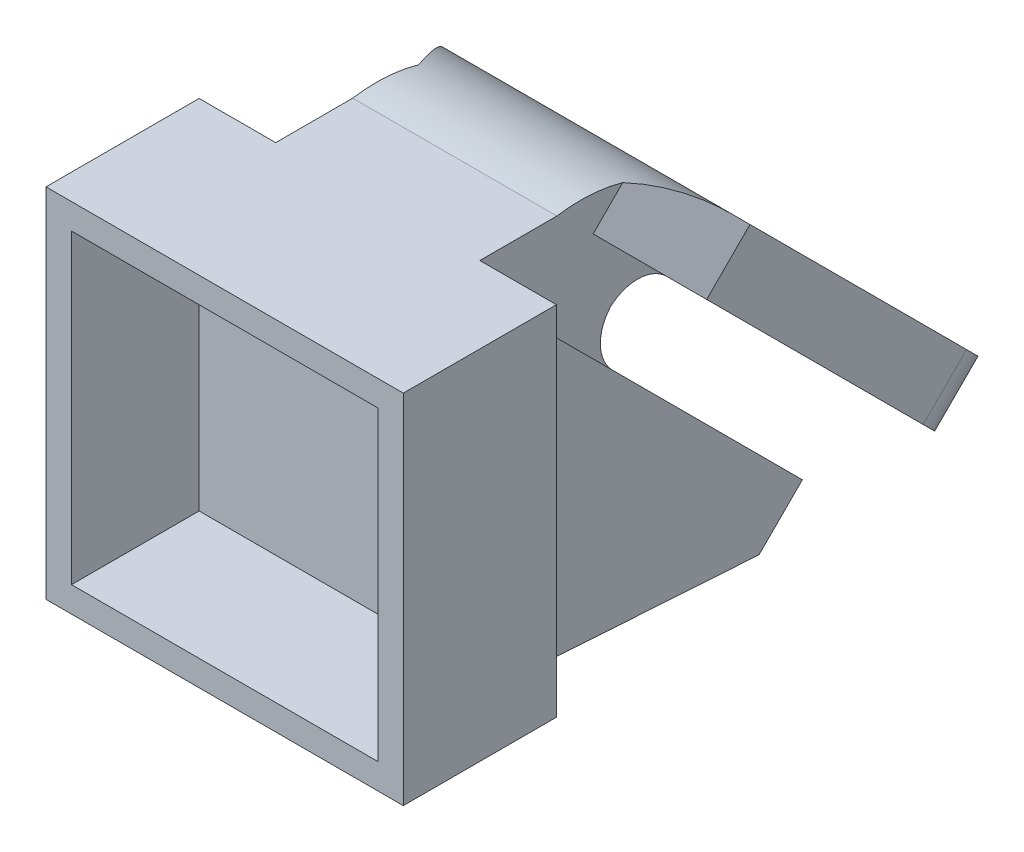
SolidWorks part; units mm, degrees
ref_plane "Piano frontale" through (0, 0, 0) normal (0, 0, 1) x (1, 0, 0)
ref_plane "Piano superiore" through (0, 0, 0) normal (0, 1, 0) x (1, 0, 0)
ref_plane "Piano destro" through (0, 0, 0) normal (1, 0, 0) x (0, 0, -1)
sketch "Schizzo1" plane through (0, 0, 0) normal (0, 0, 1) x (1, 0, 0)
  line L1 (30, -30) -> (-30, -30)
  line L2 (30, -30) -> (30, 30)
  line L3 (30, 30) -> (-30, 30)
  line L4 (-30, -30) -> (-30, 30)
  line L5 (30, -30) -> (-30, 30) construction
  line L6 (30, 30) -> (-30, -30) construction
  line L7 (35, -35) -> (-35, -35)
  line L8 (35, -35) -> (35, 35)
  line L9 (35, 35) -> (-35, 35)
  line L10 (-35, -35) -> (-35, 35)
  line L11 (35, -35) -> (-35, 35) construction
  line L12 (35, 35) -> (-35, -35) construction
  point P0 (0, 0)
  point P6 (0, 0)
  dimension "D1" = 60
  dimension "D2" = 60
  dimension "D3" = 5
  dimension "D4" = 5
extrude "Estrusione-Estrusione1" add sketch "Schizzo1" along normal blind 30
sketch "Schizzo2" plane through (0, 0, 0) normal (0, 0, 1) x (1, 0, 0)
  line L0 (35, 35) -> (-35, 35) construction
  line L1 (35, -35) -> (-35, -35)
  line L2 (35, -35) -> (35, 35)
  line L3 (35, 35) -> (-35, 35)
  line L4 (-35, -35) -> (-35, 35)
  line L5 (35, -35) -> (-35, 35) construction
  line L6 (35, 35) -> (-35, -35) construction
  line L7 (-35, 35) -> (-35, -35) construction
  point P0 (0, 0)
extrude "Estrusione-Estrusione2" add sketch "Schizzo2" along normal blind 5
sketch "Schizzo3" plane through (0, 0, 0) normal (0, 0, -1) x (-1, 0, 0)
  line L0 (-35, 35) -> (35, 35) construction
  line L1 (-20, 35) -> (20, 35)
  line L2 (-20, 35) -> (-20, 15)
  line L3 (-20, 15) -> (20, 15)
  line L4 (20, 35) -> (20, 15)
  point P6 (0, 15)
  dimension "D1" = 20
  dimension "D2" = 40
extrude "Estrusione-Estrusione3" add sketch "Schizzo3" along normal blind 25
chamfer "Smusso1" distance 20 angle 45 1 edges at (0, 15, -25)
ref_plane "Piano1" through (0, 5, 5) normal (0, -0.7071, -0.7071) x (-1, 0, 0)
sketch "Schizzo4" plane through (0, 5, 5) normal (0, -0.7071, -0.7071) x (-1, 0, 0)
  line L0 (20, 42.4264) -> (20, 14.1421) construction
  line L9 (20, 42.4264) -> (-20, 42.4264) construction
  line L10 (-30, 47.7843) -> (30, 47.7843)
  line L11 (-30, 47.7843) -> (-30, 35.7843)
  line L12 (-30, 35.7843) -> (30, 35.7843)
  line L13 (30, 47.7843) -> (30, 35.7843)
  line L14 (-20, 20.7843) -> (20, 20.7843)
  line L15 (-20, 20.7843) -> (-20, 8.7843)
  line L16 (-20, 8.7843) -> (20, 8.7843)
  line L17 (20, 20.7843) -> (20, 8.7843)
  line L18 (0, 35.7843) -> (0, 20.7843) construction
  point P8 (0, 28.2843)
  point P12 (20, 28.2843)
  point P15 (0, 42.4264)
  point P16 (0, 35.7843)
  point P17 (0, 20.7843)
  dimension "D1" = 60
  dimension "D2" = 12
  dimension "D3" = 12
  dimension "D4" = 15
  dimension "D5" = 40
extrude "Estrusione-Estrusione4" add sketch "Schizzo4" along normal blind 80
sketch "Schizzo19" plane through (0, -51.5685, -51.5685) normal (0, -0.7071, -0.7071) x (1, 0, 0)
  line L1 (-30, -35.7843) -> (30, -35.7843)
  line L2 (-30, -35.7843) -> (-30, -47.7843)
  line L3 (-30, -47.7843) -> (30, -47.7843)
  line L4 (30, -35.7843) -> (30, -47.7843)
extrude "Estrusione-Estrusione7" add sketch "Schizzo19" along normal blind 10
sketch "Schizzo6" plane through (0, 25.3033, -25.3033) normal (0, 0.7071, -0.7071) x (1, 0, 0)
  line L1 (-30, 82.9289) -> (30, 82.9289) construction
  circle A0 centre (0, 52.9289) radius 27.575
  dimension "D1" = 55.15
  dimension "D2" = 30
extrude "Taglio-Estrusione1" cut sketch "Schizzo6" along normal blind 9 from offset 3
sketch "Schizzo7" plane through (0, 25.3033, -25.3033) normal (0, 0.7071, -0.7071) x (1, 0, 0)
  circle A0 centre (0, 52.9289) radius 23.7
  circle A2 centre (0, 52.9289) radius 27.575 construction
  dimension "D1" = 47.4
extrude "Taglio-Estrusione2" cut sketch "Schizzo7" along normal up to next
sketch "Schizzo9" plane through (0, 6.2114, -6.2114) normal (0, -0.7071, 0.7071) x (1, 0, 0)
  line L0 (20, -72.9289) -> (-20, -32.9289) construction
  line L2 (20, -72.9289) -> (-20, -72.9289) construction
  line L3 (20, -72.9289) -> (-20, -72.9289) construction
  line L5 (-20, -72.9289) -> (-20, 7.0711) construction
  line L6 (20, -72.9289) -> (20, 7.0711) construction
  circle A0 centre (0, -52.9289) radius 11.1
  point P11 (0, -52.9289)
  dimension "D1" = 22.2
  dimension "D2" = 45
extrude "Taglio-Estrusione3" cut sketch "Schizzo9" against normal blind 2.5 contours A0
sketch "Schizzo10" plane through (0, 6.2114, -6.2114) normal (0, -0.7071, 0.7071) x (1, 0, 0)
  circle A0 centre (0, -52.9289) radius 14 construction
  circle A1 centre (-9.8941, -43.0241) radius 1.5
  circle A2 centre (9.8941, -43.0241) radius 1.5
  circle A3 centre (9.8941, -62.8338) radius 1.5
  circle A4 centre (-9.8941, -62.8338) radius 1.5
  dimension "D1" = 28
  dimension "D2" = 3
  dimension "D3" = 3
  dimension "D4" = 3
  dimension "D5" = 3
  dimension "D6" = 19.7883
extrude "Taglio-Estrusione4" cut sketch "Schizzo10" against normal up to next
sketch "Schizzo11" plane through (0, 14.6967, -14.6967) normal (0, 0.7071, -0.7071) x (1, 0, 0)
  circle A0 centre (-9.8941, 62.8338) radius 2.8
  circle A1 centre (-9.8941, 43.0241) radius 2.8
  circle A2 centre (9.8941, 62.8338) radius 2.8
  circle A3 centre (9.8941, 43.0241) radius 2.8
  dimension "D1" = 5.6
extrude "Taglio-Estrusione5" cut sketch "Schizzo11" against normal blind 3.2
sketch "Schizzo12" plane through (0, 7.9792, -7.9792) normal (0, -0.7071, 0.7071) x (1, 0, 0)
  circle A0 centre (0, -52.9289) radius 5
  dimension "D1" = 10
extrude "Taglio-Estrusione6" cut sketch "Schizzo12" against normal up to next
sketch "Schizzo13" plane through (0, 5, 5) normal (0, 0.7071, 0.7071) x (1, 0, 0)
  line L1 (-20, 47.7843) -> (20, 47.7843)
  line L2 (-20, 47.7843) -> (-20, -6.2157)
  line L3 (-20, -6.2157) -> (20, -6.2157)
  line L4 (20, 47.7843) -> (20, -6.2157)
  line L5 (20, 42.4264) -> (20, 24.7487) construction
  line L6 (-20, 42.4264) -> (-20, 24.7487) construction
  line L7 (-30, 47.7843) -> (30, 47.7843) construction
  dimension "D1" = 54
extrude "Estrusione-Estrusione5" add sketch "Schizzo13" along normal blind 7
sketch "Schizzo17" plane through (0, 5, 5) normal (0, -0.7071, -0.7071) x (1, 0, 0)
  line L1 (-20, 9.2157) -> (20, 9.2157)
  line L2 (-20, 9.2157) -> (-20, -35.7843)
  line L3 (-20, -35.7843) -> (20, -35.7843)
  line L4 (20, 9.2157) -> (20, -35.7843)
  line L10 (-20, -8.7843) -> (-20, -20.7843) construction
  dimension "D1" = 45
extrude "Estrusione-Estrusione6" add sketch "Schizzo17" along normal blind 15
fillet "Raccordo4" radius 10 4 edges at (-20, -41.1145, -62.0226) (20, -41.1145, -62.0226) (-30, -29.0937, -88.1856) (30, -29.0937, -88.1856)
sketch "Schizzo18" plane through (0, 0, 5) normal (0, 0, 1) x (1, 0, 0)
  line L1 (-30, 30) -> (30, 30)
  line L2 (-30, 30) -> (-30, -30)
  line L3 (-30, -30) -> (30, -30)
  line L4 (30, 30) -> (30, -30)
extrude "Taglio-Estrusione10" cut sketch "Schizzo18" along normal through all
chamfer "Smusso2" distance 20 angle 30 2 edges at (-30, 34.5459, -24.5459) (30, 34.5459, -24.5459) first distance on face at (-30, 6.2617, -52.8302) first distance on face at (30, 6.2617, -52.8302)
fillet "Raccordo5" radius 30 1 edges at (0, 43.7383, -23.8388)
fillet "Raccordo6" radius 8 2 edges at (0, 9.0901, -20.3033) (0, 19.6967, -30.9099)
fillet "Raccordo7" radius 15 2 edges at (0, -11.2132, 0) (0, 0.6048, -11.818)
sketch "Schizzo20" plane through (0, 0, 0) normal (1, 0, 0) x (0, 0, -1)
  line L0 (0, -35) -> (50.7089, -38.2861)
  line L8 (0, 29.3934) -> (0, -35)
  line L11 (0, -35) -> (0, 35) construction
  line L13 (50.7089, -38.2861) -> (59.1942, -29.8008)
  line L14 (59.1942, -29.8008) -> (0, 29.3934)
extrude "Estrusione-Estrusione8" add sketch "Schizzo20" along normal blind 4 from surface starting at face at (20, 5.5908, -23.8503)
sketch "Schizzo21" plane through (0, 0, 0) normal (1, 0, 0) x (0, 0, -1)
  line L0 (50.7089, -38.2861) -> (0, -35)
  line L2 (0, 35) -> (0, -35) construction
  line L4 (0, -35) -> (0, 29.3934)
  line L5 (50.7089, -38.2861) -> (59.1942, -29.8008)
  line L6 (59.1942, -29.8008) -> (0, 29.3934)
  line L7 (0, -35) -> (0, 35) construction
  line L8 (0, 29.3934) -> (25.9602, 3.4332) construction
  line L9 (66.2652, -36.8718) -> (59.1942, -29.8008) construction
extrude "Estrusione-Estrusione9" add sketch "Schizzo21" against normal blind 4 from surface starting at face at (-20, 5.5908, -23.8503)
